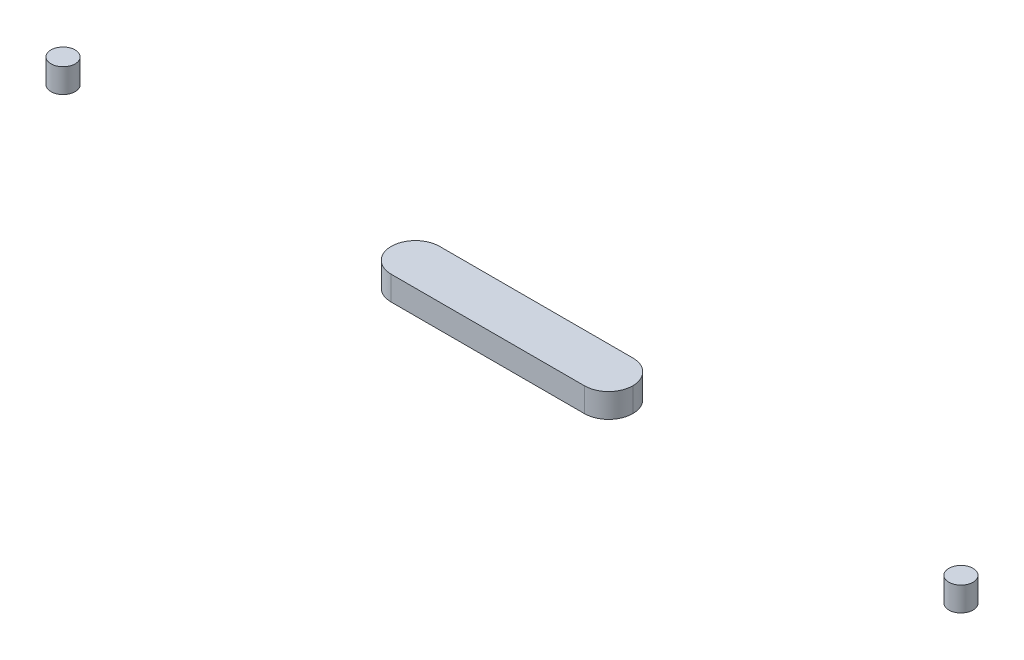
SolidWorks part; units mm, degrees
ref_plane "Front Plane" through (0, 0, 0) normal (0, 0, 1) x (1, 0, 0)
ref_plane "Top Plane" through (0, 0, 0) normal (0, 1, 0) x (1, 0, 0)
ref_plane "Right Plane" through (0, 0, 0) normal (1, 0, 0) x (0, 0, -1)
sketch "Sketch1" plane through (0, 0, 0) normal (0, 1, 0) x (1, 0, 0)
  line L1 (25, -5) -> (-25, -5)
  line L2 (25, -5) -> (25, 5)
  line L3 (25, 5) -> (-25, 5)
  line L4 (-25, -5) -> (-25, 5)
  line L5 (0, 5) -> (0, -5) construction
  line L6 (25, 0) -> (-25, 0) construction
  circle A0 centre (-92.9316, 0) radius 2.5
  circle A1 centre (92.9316, 0) radius 2.5
  point P0 (0, 0)
  dimension "D1" = 50
  dimension "D2" = 10
extrude "Boss-Extrude1" add sketch "Sketch1" along normal blind 5
fillet "Fillet1" radius 5 4 edges at (-25, 2.5, -5) (25, 2.5, -5) (25, 2.5, 5) (-25, 2.5, 5)
